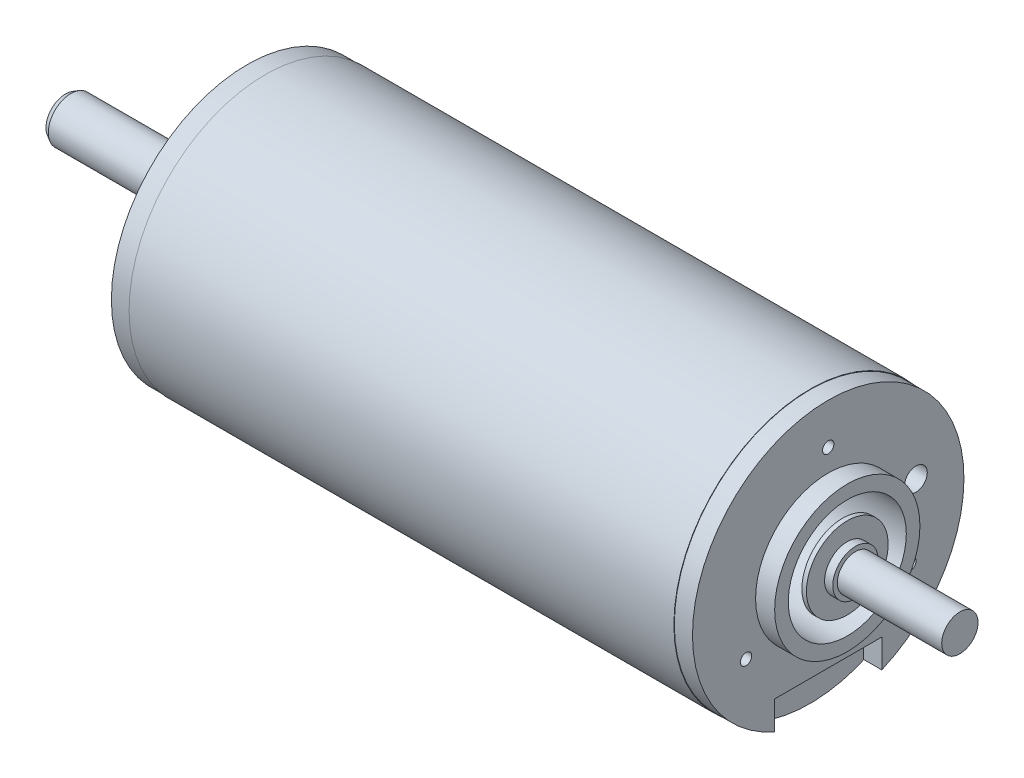
SolidWorks part; units mm, degrees
ref_plane "Front Plane" through (0, 0, 0) normal (0, 0, 1) x (1, 0, 0)
ref_plane "Top Plane" through (0, 0, 0) normal (0, 1, 0) x (1, 0, 0)
ref_plane "Right Plane" through (0, 0, 0) normal (1, 0, 0) x (0, 0, -1)
ref_plane "Plane1" through (0, 0, 0) normal (0, 0, -1) x (-1, 0, 0)
sketch "Sketch1" plane through (0, 0, 0) normal (0, 0, -1) x (-1, 0, 0)
  line L0 (-62, 15) -> (-62, 0)
  line L1 (-62, 0) -> (-2, 0)
  line L2 (-2, 0) -> (-2, 15)
  line L3 (-2, 15) -> (-62, 15)
  line L4 (-62, 0) -> (-2, 0) construction
revolve "Revolve1" add sketch "Sketch1" angle 360 about L4 reverse direction yes
sketch "Sketch2" plane through (62, 0, 0) normal (1, 0, 0) x (0, 0, -1)
  line L0 (5.9, -13.7365) -> (5.9, -10.6)
  line L1 (5.9, -10.6) -> (-5.9, -10.6)
  line L2 (-5.9, -10.6) -> (-5.9, -13.7365)
  arc A0 (-5.9, -13.7365) -> (5.9, -13.7365) centre (0, 0) cw
extrude "Boss-Extrude1" add sketch "Sketch2" along normal blind 2
sketch "Sketch3" plane through (64, 0, 0) normal (1, 0, 0) x (0, 0, -1)
  circle A0 centre (0, 0) radius 8
extrude "Boss-Extrude2" add sketch "Sketch3" along normal blind 2.1
hole_wizard "Hole1" positions "Sketch5" profile "Sketch4" legacy
sketch "Sketch5" plane through (66.1, 0, 0) normal (1, 0, 0) x (0, 0, -1)
  point P0 (0, 0)
sketch "Sketch4" plane through (66.1, 0, 0) normal (0, 1, 0) x (0, 0, -1)
  line L0 (0, 0) -> (0, 0.5)
  line L1 (0, 0.5) -> (6.5, 0.5)
  line L2 (6.5, 0.5) -> (6.5, 0)
  line L3 (6.5, 0) -> (0, 0)
  line L4 (0, 110) -> (0, -10) construction
  dimension "Diameter" = 13
  dimension "Depth" = 0.5
sketch "Sketch6" plane through (2, 0, 0) normal (-1, 0, 0) x (0, 0, 1)
  circle A0 centre (0, 0) radius 14.95
extrude "Boss-Extrude3" add sketch "Sketch6" along normal blind 2
sketch "Sketch7" plane through (0, 0, 0) normal (-1, 0, 0) x (0, 0, 1)
  circle A0 centre (0, 0) radius 8
extrude "Boss-Extrude4" add sketch "Sketch7" along normal blind 1.2
hole_wizard "Hole2" positions "Sketch9" profile "Sketch8" legacy
sketch "Sketch9" plane through (-1.2, 0, 0) normal (-1, 0, 0) x (0, 0, 1)
  point P0 (0, 0)
sketch "Sketch8" plane through (-1.2, 0, 0) normal (0, 1, 0) x (0, 0, 1)
  line L0 (0, 0) -> (0, 67.3)
  line L1 (0, 67.3) -> (6.5, 67.3)
  line L2 (6.5, 67.3) -> (6.5, 0)
  line L3 (6.5, 0) -> (0, 0)
  line L4 (0, 110) -> (0, -10) construction
  dimension "Diameter" = 13
  dimension "Depth" = 67.3
sketch "Sketch10" plane through (0, 0, 0) normal (0, 0, -1) x (-1, 0, 0)
  line L0 (0.7, 4.5) -> (0.7, 0)
  line L1 (0.7, 0) -> (20, 0)
  line L2 (20, 0) -> (20, 2.5)
  line L3 (20, 2.5) -> (1.2, 2.5)
  line L4 (1.2, 2.5) -> (1.2, 4.5)
  line L5 (1.2, 4.5) -> (0.7, 4.5)
  line L6 (0.7, 0) -> (20, 0) construction
revolve "Revolve2" add sketch "Sketch10" angle 360 about L6 reverse direction yes
sketch "Sketch11" plane through (0, 0, 0) normal (0, 0, -1) x (-1, 0, 0)
  line L0 (-78.5, 2) -> (-78.5, 0)
  line L1 (-78.5, 0) -> (-65.6, 0)
  line L2 (-65.6, 0) -> (-65.6, 4.5)
  line L3 (-65.6, 4.5) -> (-66.1, 4.5)
  line L4 (-66.1, 4.5) -> (-66.1, 2.5)
  line L5 (-66.1, 2.5) -> (-67, 2.5)
  line L6 (-67, 2.5) -> (-67, 2)
  line L7 (-67, 2) -> (-78.5, 2)
  line L8 (-78.5, 0) -> (-65.6, 0) construction
revolve "Revolve3" add sketch "Sketch11" angle 360 about L8 reverse direction yes
hole_wizard "Hole3" positions "Sketch13" profile "Sketch12" legacy
sketch "Sketch13" plane through (0, 0, 0) normal (-1, 0, 0) x (0, 0, 1)
  point P0 (8.6603, -5)
sketch "Sketch12" plane through (0, -5, 8.6603) normal (0, 1, 0) x (0, 0, 1)
  line L0 (0, 0) -> (0, 2)
  line L1 (0, 2) -> (1.25, 2)
  line L2 (1.25, 2) -> (1.25, 0)
  line L3 (1.25, 0) -> (0, 0)
  line L4 (0, 110) -> (0, -10) construction
  dimension "Diameter" = 2.5
  dimension "Depth" = 2
hole_wizard "Hole4" positions "Sketch15" profile "Sketch14" legacy
sketch "Sketch15" plane through (64, 0, 0) normal (1, 0, 0) x (0, 0, -1)
  point P0 (9.6593, 2.5882)
sketch "Sketch14" plane through (64, 2.5882, -9.6593) normal (0, 1, 0) x (0, 0, -1)
  line L0 (0, 0) -> (0, 2)
  line L1 (0, 2) -> (1.25, 2)
  line L2 (1.25, 2) -> (1.25, 0)
  line L3 (1.25, 0) -> (0, 0)
  line L4 (0, 110) -> (0, -10) construction
  dimension "Diameter" = 2.5
  dimension "Depth" = 2
hole_wizard "Hole5" positions "Sketch17" profile "Sketch16" legacy
sketch "Sketch17" plane through (0, 0, 0) normal (-1, 0, 0) x (0, 0, 1)
  point P0 (11, 0)
sketch "Sketch16" plane through (0, 0, 11) normal (0, 1, 0) x (0, 0, 1)
  line L0 (0, 0) -> (0, 7.2511)
  line L1 (0, 7.2511) -> (1.25, 6.5)
  line L2 (1.25, 6.5) -> (1.25, 0)
  line L4 (1.25, 0) -> (0, 0)
  line L6 (0, 7.2511) -> (-1.25, 6.5) construction
  line L7 (0, -4.2442) -> (0, 117.3081) construction
  dimension "Diameter" = 2.5
  dimension "Depth" = 6.5
  dimension "Drill Angle" = 118
hole_wizard "Hole6" positions "Sketch19" profile "Sketch18" legacy
sketch "Sketch19" plane through (0, 0, 0) normal (-1, 0, 0) x (0, 0, 1)
  point P0 (0, 11)
sketch "Sketch18" plane through (0, 11, 0) normal (0, 1, 0) x (0, 0, 1)
  line L0 (0, 0) -> (0, 7.2511)
  line L1 (0, 7.2511) -> (1.25, 6.5)
  line L2 (1.25, 6.5) -> (1.25, 0)
  line L4 (1.25, 0) -> (0, 0)
  line L6 (0, 7.2511) -> (-1.25, 6.5) construction
  line L7 (0, -4.2442) -> (0, 117.3081) construction
  dimension "Diameter" = 2.5
  dimension "Depth" = 6.5
  dimension "Drill Angle" = 118
hole_wizard "Hole7" positions "Sketch21" profile "Sketch20" legacy
sketch "Sketch21" plane through (0, 0, 0) normal (-1, 0, 0) x (0, 0, 1)
  point P0 (-11, 0)
sketch "Sketch20" plane through (0, 0, -11) normal (0, 1, 0) x (0, 0, 1)
  line L0 (0, 0) -> (0, 7.2511)
  line L1 (0, 7.2511) -> (1.25, 6.5)
  line L2 (1.25, 6.5) -> (1.25, 0)
  line L4 (1.25, 0) -> (0, 0)
  line L6 (0, 7.2511) -> (-1.25, 6.5) construction
  line L7 (0, -4.2442) -> (0, 117.3081) construction
  dimension "Diameter" = 2.5
  dimension "Depth" = 6.5
  dimension "Drill Angle" = 118
hole_wizard "Hole8" positions "Sketch23" profile "Sketch22" legacy
sketch "Sketch23" plane through (0, 0, 0) normal (-1, 0, 0) x (0, 0, 1)
  point P0 (0, -11)
sketch "Sketch22" plane through (0, -11, 0) normal (0, 1, 0) x (0, 0, 1)
  line L0 (0, 0) -> (0, 7.2511)
  line L1 (0, 7.2511) -> (1.25, 6.5)
  line L2 (1.25, 6.5) -> (1.25, 0)
  line L4 (1.25, 0) -> (0, 0)
  line L6 (0, 7.2511) -> (-1.25, 6.5) construction
  line L7 (0, -4.2442) -> (0, 117.3081) construction
  dimension "Diameter" = 2.5
  dimension "Depth" = 6.5
  dimension "Drill Angle" = 118
hole_wizard "Hole9" positions "Sketch25" profile "Sketch24" legacy
sketch "Sketch25" plane through (64, 0, 0) normal (1, 0, 0) x (0, 0, -1)
  point P0 (0, 10.45)
sketch "Sketch24" plane through (64, 10.45, 0) normal (0, 1, 0) x (0, 0, -1)
  line L0 (0, 0) -> (0, 3.1755)
  line L1 (0, 3.1755) -> (0.625, 2.8)
  line L2 (0.625, 2.8) -> (0.625, 0)
  line L4 (0.625, 0) -> (0, 0)
  line L6 (0, 3.1755) -> (-0.625, 2.8) construction
  line L7 (0, -4.2442) -> (0, 117.3081) construction
  dimension "Diameter" = 1.25
  dimension "Depth" = 2.8
  dimension "Drill Angle" = 118
hole_wizard "Hole10" positions "Sketch27" profile "Sketch26" legacy
sketch "Sketch27" plane through (64, 0, 0) normal (1, 0, 0) x (0, 0, -1)
  point P0 (9.05, -5.225)
sketch "Sketch26" plane through (64, -5.225, -9.05) normal (0, 1, 0) x (0, 0, -1)
  line L0 (0, 0) -> (0, 3.1755)
  line L1 (0, 3.1755) -> (0.625, 2.8)
  line L2 (0.625, 2.8) -> (0.625, 0)
  line L4 (0.625, 0) -> (0, 0)
  line L6 (0, 3.1755) -> (-0.625, 2.8) construction
  line L7 (0, -4.2442) -> (0, 117.3081) construction
  dimension "Diameter" = 1.25
  dimension "Depth" = 2.8
  dimension "Drill Angle" = 118
hole_wizard "Hole11" positions "Sketch29" profile "Sketch28" legacy
sketch "Sketch29" plane through (64, 0, 0) normal (1, 0, 0) x (0, 0, -1)
  point P0 (-9.05, -5.225)
sketch "Sketch28" plane through (64, -5.225, 9.05) normal (0, 1, 0) x (0, 0, -1)
  line L0 (0, 0) -> (0, 3.1755)
  line L1 (0, 3.1755) -> (0.625, 2.8)
  line L2 (0.625, 2.8) -> (0.625, 0)
  line L4 (0.625, 0) -> (0, 0)
  line L6 (0, 3.1755) -> (-0.625, 2.8) construction
  line L7 (0, -4.2442) -> (0, 117.3081) construction
  dimension "Diameter" = 1.25
  dimension "Depth" = 2.8
  dimension "Drill Angle" = 118
chamfer "Chamfer1" distance 0.3464 angle 60 1 edges at (-20, 0, 2.5) first distance on face at (-20, 0, 2.5)
